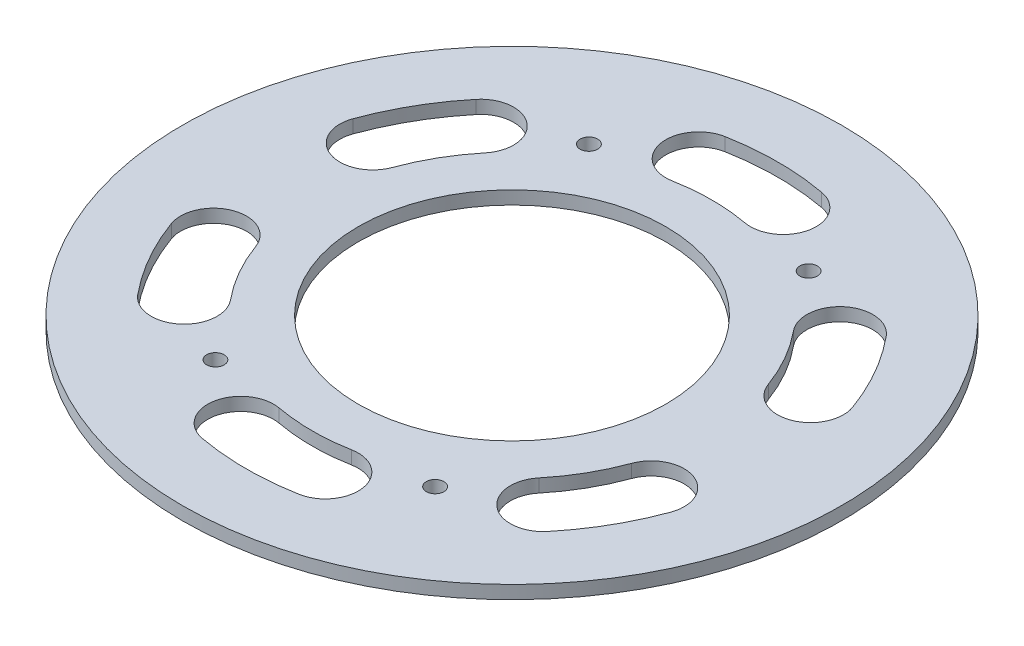
SolidWorks part; units mm, degrees
material "5052-H34"
ref_plane "正面" through (0, 0, 0) normal (0, 0, 1) x (1, 0, 0)
ref_plane "平面" through (0, 0, 0) normal (0, 1, 0) x (1, 0, 0)
ref_plane "右側面" through (0, 0, 0) normal (1, 0, 0) x (0, 0, -1)
sketch "ｽｹｯﾁ1" plane through (0, 0, 0) normal (0, 1, 0) x (1, 0, 0)
  line L0 (0, 42.5) -> (0, 0) construction
  line L1 (-25, 42.5) -> (25, 42.5) construction
  line L2 (-25, 42.5) -> (-25, -42.5) construction
  line L3 (-25, -42.5) -> (25, -42.5) construction
  line L4 (25, 42.5) -> (25, -42.5) construction
  line L5 (-25, 42.5) -> (25, -42.5) construction
  line L6 (-25, -42.5) -> (25, 42.5) construction
  line L7 (0, 0) -> (25, 0) construction
  circle A0 centre (0, 0) radius 75
  circle A1 centre (25, 42.5) radius 2
  circle A2 centre (-25, 42.5) radius 2
  circle A3 centre (25, -42.5) radius 2
  circle A4 centre (-25, -42.5) radius 2
  circle A5 centre (0, 0) radius 35
  dimension "D1" = 150
  dimension "D4" = 4
  dimension "D5" = 70
  dimension "D2" = 50
  dimension "D3" = 85
extrude "ﾎﾞｽ - 押し出し1" add sketch "ｽｹｯﾁ1" along normal blind 3
sketch "ｽｹｯﾁ2" plane through (0, 3, 0) normal (0, 1, 0) x (1, 0, 0)
  line L0 (0, 0) -> (0, 75) construction
  line L1 (0, 0) -> (53, 0) construction
  line L2 (40.8758, 33.7367) -> (0, 0) construction
  line L3 (0, 0) -> (0, -53) construction
  line L4 (9.6271, -52.1183) -> (0, 0) construction
  line L5 (25, 42.5) -> (0, 0) construction
  line L6 (9.6271, 52.1183) -> (0, 0) construction
  line L7 (49.8037, 18.1271) -> (0, 0) construction
  circle A0 centre (0, 0) radius 75 construction
  arc A1 (40.8758, 33.7367) -> (49.8037, 18.1271) centre (0, 0) cw construction
  arc A6 (56.8514, 20.6922) -> (46.6601, 38.5108) centre (0, 0) ccw
  arc A11 (9.6271, -52.1183) -> (-9.6271, -52.1183) centre (0, 0) cw construction
  arc A12 (-10.9895, -59.4935) -> (10.9895, -59.4935) centre (0, 0) ccw
  arc A13 (-8.2648, -44.7431) -> (8.2648, -44.7431) centre (0, 0) ccw
  arc A14 (-8.2648, -44.7431) -> (-10.9895, -59.4935) centre (-9.6271, -52.1183) ccw
  arc A15 (10.9895, -59.4935) -> (8.2648, -44.7431) centre (9.6271, -52.1183) ccw
  arc A16 (9.6271, 52.1183) -> (-9.6271, 52.1183) centre (0, 0) ccw construction
  arc A17 (-10.9895, 59.4935) -> (10.9895, 59.4935) centre (0, 0) cw
  arc A18 (-8.2648, 44.7431) -> (8.2648, 44.7431) centre (0, 0) cw
  arc A19 (-8.2648, 44.7431) -> (-10.9895, 59.4935) centre (-9.6271, 52.1183) cw
  arc A20 (10.9895, 59.4935) -> (8.2648, 44.7431) centre (9.6271, 52.1183) cw
  arc A21 (42.756, 15.5619) -> (35.0915, 28.9627) centre (0, 0) ccw
  arc A22 (42.756, 15.5619) -> (56.8514, 20.6922) centre (49.8037, 18.1271) ccw
  arc A23 (46.6601, 38.5108) -> (35.0915, 28.9627) centre (40.8758, 33.7367) ccw
  arc A24 (40.8758, -33.7367) -> (49.8037, -18.1271) centre (0, 0) ccw construction
  arc A25 (56.8514, -20.6922) -> (46.6601, -38.5108) centre (0, 0) cw
  arc A26 (42.756, -15.5619) -> (35.0915, -28.9627) centre (0, 0) cw
  arc A27 (42.756, -15.5619) -> (56.8514, -20.6922) centre (49.8037, -18.1271) cw
  arc A28 (46.6601, -38.5108) -> (35.0915, -28.9627) centre (40.8758, -33.7367) cw
  arc A29 (-40.8758, -33.7367) -> (-49.8037, -18.1271) centre (0, 0) cw construction
  arc A30 (-56.8514, -20.6922) -> (-46.6601, -38.5108) centre (0, 0) ccw
  arc A31 (-42.756, -15.5619) -> (-35.0915, -28.9627) centre (0, 0) ccw
  arc A32 (-42.756, -15.5619) -> (-56.8514, -20.6922) centre (-49.8037, -18.1271) ccw
  arc A33 (-46.6601, -38.5108) -> (-35.0915, -28.9627) centre (-40.8758, -33.7367) ccw
  arc A34 (-40.8758, 33.7367) -> (-49.8037, 18.1271) centre (0, 0) ccw construction
  arc A35 (-56.8514, 20.6922) -> (-46.6601, 38.5108) centre (0, 0) cw
  arc A36 (-42.756, 15.5619) -> (-35.0915, 28.9627) centre (0, 0) cw
  arc A37 (-42.756, 15.5619) -> (-56.8514, 20.6922) centre (-49.8037, 18.1271) cw
  arc A38 (-46.6601, 38.5108) -> (-35.0915, 28.9627) centre (-40.8758, 33.7367) cw
  point P8 (46.0066, 26.3133)
  point P19 (46.0066, -26.3133)
  point P26 (0, -53)
  point P35 (0, 53)
  point P45 (-46.0066, -26.3133)
  point P52 (-46.0066, 26.3133)
  dimension "D2" = 7.5
  dimension "D1" = 53
  dimension "D3" = 20
  dimension "D4" = 20
  dimension "D5" = 20
extrude "ｶｯﾄ - 押し出し1" cut sketch "ｽｹｯﾁ2" against normal through all
